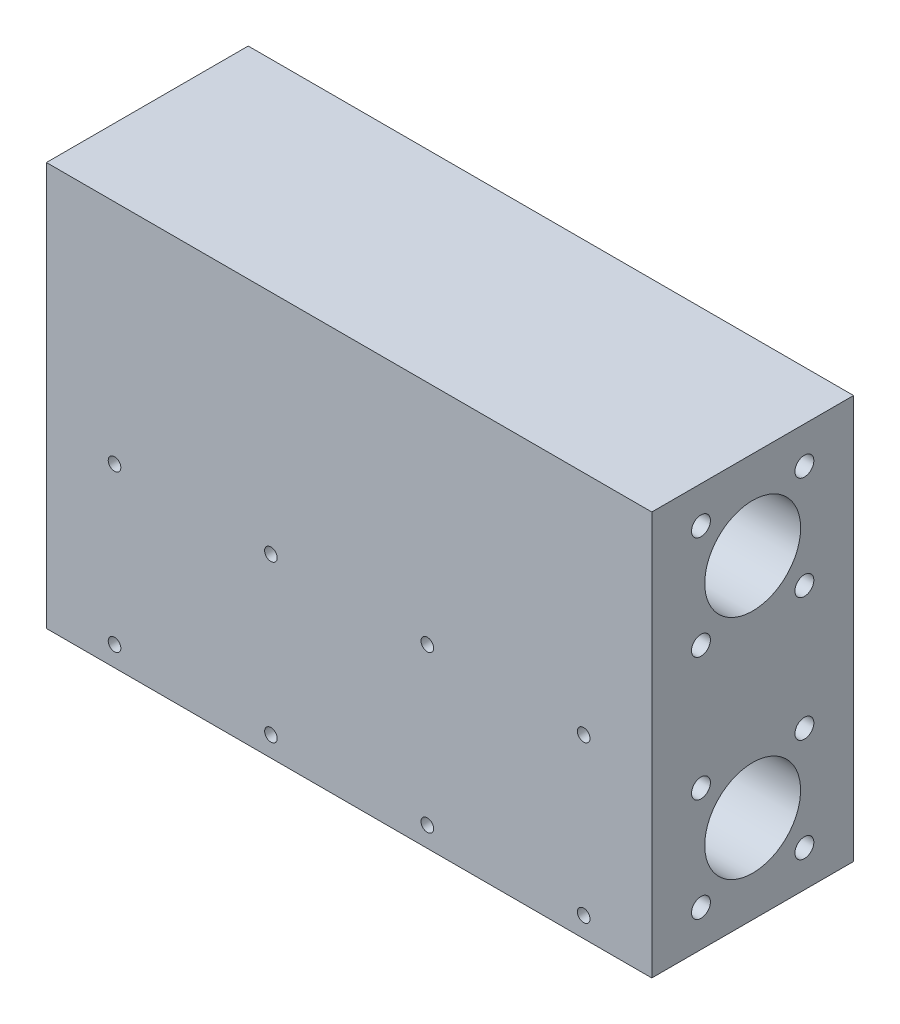
SolidWorks part; units mm, degrees
ref_plane "Front Plane" through (0, 0, 0) normal (0, 0, 1) x (1, 0, 0)
ref_plane "Top Plane" through (0, 0, 0) normal (0, 1, 0) x (1, 0, 0)
ref_plane "Right Plane" through (0, 0, 0) normal (1, 0, 0) x (0, 0, -1)
sketch "Sketch1" plane through (0, 0, 0) normal (0, 0, 1) x (1, 0, 0)
  line L1 (0, 0) -> (120, 0)
  line L2 (0, 0) -> (0, 80)
  line L3 (0, 80) -> (120, 80)
  line L4 (120, 0) -> (120, 80)
  dimension "D1" = 80
  dimension "D2" = 120
extrude "Boss-Extrude1" add sketch "Sketch1" along normal blind 40 contours L3 L4 L1 L2
sketch "Sketch2" plane through (0, 0, 0) normal (-1, 0, 0) x (0, 0, 1)
  line L0 (20, 80) -> (20, 0) construction
  line L1 (40, 80) -> (0, 80) construction
  line L2 (40, 0) -> (0, 0) construction
  line L3 (40, 40) -> (0, 40) construction
  line L4 (40, 0) -> (40, 80) construction
  line L5 (0, 0) -> (0, 80) construction
  line L6 (0, 62.5) -> (40, 62.5) construction
  line L7 (0, 17.5) -> (40, 17.5) construction
  circle A1 centre (30.25, 72.75) radius 1.85
  circle A2 centre (9.75, 72.75) radius 1.85
  circle A3 centre (30.25, 52.25) radius 1.85
  circle A4 centre (9.75, 52.25) radius 1.85
  circle A5 centre (9.75, 27.75) radius 1.85
  circle A6 centre (30.25, 27.75) radius 1.85
  circle A7 centre (30.25, 7.25) radius 1.85
  circle A9 centre (9.75, 7.25) radius 1.85
  dimension "D4" = 3.7
  dimension "D1" = 22.5
  dimension "D2" = 9.75
  dimension "D3" = 7.25
extrude "linear-bearing-screw-cuts" cut sketch "Sketch2" against normal blind 14
sketch "Sketch3" plane through (0, 0, 0) normal (-1, 0, 0) x (0, 0, 1)
  line L0 (20, 80) -> (20, 0) construction
  line L1 (40, 80) -> (0, 80) construction
  line L2 (40, 0) -> (0, 0) construction
  line L3 (0, 40) -> (40, 40) construction
  line L4 (0, 0) -> (0, 80) construction
  line L5 (40, 0) -> (40, 80) construction
  line L6 (0, 62.5) -> (40, 62.5) construction
  line L7 (0, 17.5) -> (40, 17.5) construction
  circle A0 centre (20, 62.5) radius 9.5
  circle A2 centre (20, 17.5) radius 9.5
  dimension "D2" = 19
  dimension "D1" = 45
extrude "linear-bearings-hole" cut sketch "Sketch3" against normal blind 55
sketch "Sketch4" plane through (120, 0, 0) normal (1, 0, 0) x (0, 0, -1)
  line L0 (-20, 80) -> (-20, 0) construction
  line L1 (-40, 80) -> (0, 80) construction
  line L2 (-40, 0) -> (0, 0) construction
  line L3 (-40, 40) -> (0, 40) construction
  line L4 (-40, 0) -> (-40, 80) construction
  line L5 (0, 0) -> (0, 80) construction
  line L6 (-40, 62.5) -> (0, 62.5) construction
  line L7 (-40, 17.5) -> (0, 17.5) construction
  circle A0 centre (-9.75, 72.75) radius 1.875
  circle A1 centre (-30.25, 72.75) radius 1.875
  circle A2 centre (-9.75, 52.25) radius 1.875
  circle A3 centre (-30.25, 52.25) radius 1.875
  circle A4 centre (-30.25, 27.75) radius 1.875
  circle A5 centre (-9.75, 27.75) radius 1.875
  circle A6 centre (-9.75, 7.25) radius 1.875
  circle A7 centre (-30.25, 7.25) radius 1.875
  dimension "D2" = 3.75
  dimension "D1" = 45
  dimension "D3" = 7.25
  dimension "D4" = 9.75
extrude "linear-bearing-screw-cuts2" cut sketch "Sketch4" against normal blind 14
sketch "Sketch5" plane through (120, 0, 0) normal (1, 0, 0) x (0, 0, -1)
  line L0 (-20, 80) -> (-20, 0) construction
  line L1 (-40, 80) -> (0, 80) construction
  line L2 (-40, 0) -> (0, 0) construction
  line L3 (0, 40) -> (-40, 40) construction
  line L4 (0, 0) -> (0, 80) construction
  line L5 (-40, 0) -> (-40, 80) construction
  line L6 (-40, 62.5) -> (0, 62.5) construction
  line L7 (-40, 17.5) -> (0, 17.5) construction
  circle A0 centre (-20, 62.5) radius 9.5
  circle A1 centre (-20, 17.5) radius 9.5
  dimension "D2" = 19
  dimension "D1" = 45
extrude "linear-bearings-hole2" cut sketch "Sketch5" against normal blind 55
sketch "Sketch10" plane through (0, 80, 0) normal (0, 1, 0) x (1, 0, 0)
  line L0 (60, 0) -> (60, -40) construction
  line L1 (0, 0) -> (120, 0) construction
  line L2 (0, -40) -> (120, -40) construction
  line L3 (75, 0) -> (75, -40) construction
  line L4 (92.5, -40) -> (97.5, -35)
  line L5 (97.5, -35) -> (82.5, -35)
  line L6 (82.5, -35) -> (87.5, -40)
  line L7 (87.5, -40) -> (92.5, -40)
  line L8 (120, -40) -> (120, 0) construction
  line L9 (67.5, -35) -> (62.5, -40)
  line L10 (52.5, -35) -> (67.5, -35)
  line L11 (57.5, -40) -> (52.5, -35)
  line L12 (62.5, -40) -> (57.5, -40)
  line L13 (37.5, -35) -> (32.5, -40)
  line L14 (22.5, -35) -> (37.5, -35)
  line L15 (27.5, -40) -> (22.5, -35)
  line L16 (32.5, -40) -> (27.5, -40)
  point P10 (90, -40)
  dimension "D1" = 45
  dimension "D2" = 15
  dimension "D3" = 5
  dimension "D4" = 30
  dimension "D5" = 45
extrude "Cut-Extrude7" [suppressed] cut sketch "Sketch10" against normal blind 60
sketch "Sketch11" plane through (0, 0, 40) normal (0, 0, 1) x (1, 0, 0)
  line L0 (0, 0) -> (120, 0) construction
  line L1 (0, 0) -> (0, 80) construction
  circle A0 centre (13.5, 35) radius 1.25
  circle A1 centre (44.5, 35) radius 1.25
  circle A2 centre (75.5, 35) radius 1.25
  circle A3 centre (106.5, 35) radius 1.25
  circle A4 centre (13.5, 4) radius 1.25
  circle A5 centre (44.5, 4) radius 1.25
  circle A6 centre (75.5, 4) radius 1.25
  circle A7 centre (106.5, 4) radius 1.25
  point P16 (0, 0)
  point P19 (0, 0)
  point P20 (0, 0)
  point P21 (0, 0)
  point P22 (0, 0)
  point P23 (0, 0)
  point P24 (0, 0)
  dimension "D7" = 2.5
  dimension "D1" = 4
  dimension "D2" = 31
  dimension "D3" = 31
  dimension "D4" = 31
  dimension "D5" = 31
  dimension "D6" = 13.5
extrude "Cut-Extrude8" cut sketch "Sketch11" against normal through all
